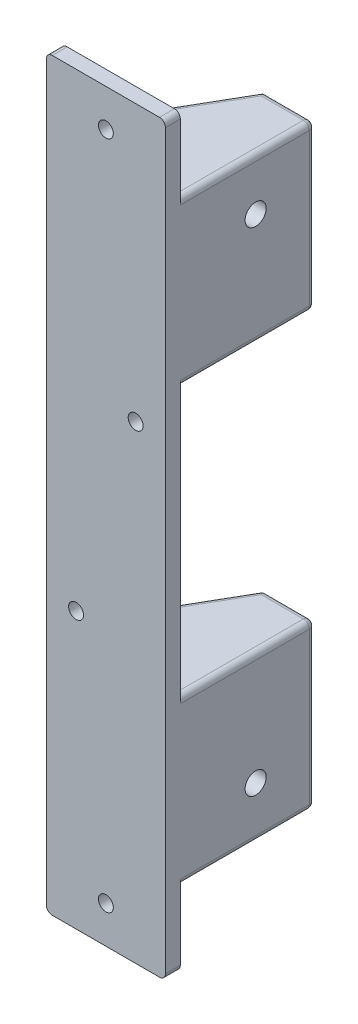
SolidWorks part; units mm, degrees
material "ABS"
ref_plane "X-Y Datum" through (0, 0, 0) normal (0, 0, 1) x (1, 0, 0)
ref_plane "X-Z Datum" through (0, 0, 0) normal (0, 1, 0) x (1, 0, 0)
ref_plane "Y-Z Datum" through (0, 0, 0) normal (1, 0, 0) x (0, 0, -1)
sketch "Sketch1" plane through (0, 0, 0) normal (0, 1, 0) x (1, 0, 0)
  line L0 (0, 0) -> (-25.4, 0)
  line L1 (-25.4, 0) -> (-25.4, 6.985)
  line L2 (-25.4, 6.985) -> (0, 50.9791)
  line L3 (0, 50.9791) -> (0, 0)
  dimension "D1" = 25.4
  dimension "D2" = 60
  dimension "D3" = 6.985
extrude "Boss-Extrude1" add sketch "Sketch1" along normal blind 127
ref_plane "Plane1" through (0, 63.5, 0) normal (0, -1, 0) x (-1, 0, 0)
sketch "Sketch2" plane through (0, 63.5, 0) normal (0, -1, 0) x (-1, 0, 0)
  line L0 (3.175, 3.175) -> (25.4, 3.175)
  line L2 (25.4, 3.175) -> (25.4, 6.985)
  line L3 (25.4, 6.985) -> (3.175, 45.4798)
  line L4 (3.175, 45.4798) -> (3.175, 3.175)
  line L5 (25.4, 3.175) -> (25.4, 0) construction
  line L6 (25.4, 0) -> (0, 0) construction
  line L7 (25.4, 6.985) -> (25.4, 0) construction
  line L9 (0, 50.9791) -> (25.4, 6.985) construction
  line L10 (0, 50.9791) -> (25.4, 6.985) construction
  line L11 (3.175, 3.175) -> (0, 3.175)
  line L12 (0, 0) -> (0, 50.9791) construction
  dimension "D1" = 3.175
extrude "Cut-Extrude1" cut sketch "Sketch2" against normal offset from surface (28.575 mm away) 3.175 from offset 31.75 contours L3 L4 L0 L2 region at (-11.1954, 63.5, -17.3815) up to face at (-12.7, 127, -14.491) offset against normal yes
extrude "Cut-Extrude2" cut sketch "Sketch2<2>" along normal offset from surface (28.575 mm away) 3.175 from offset 31.75 contours L3 L4 L0 L2 region at (-11.1954, 63.5, -17.3815) up to face at (-12.7, 0, -14.491)
sketch "Sketch2<2>" plane through (0, 63.5, 0) normal (0, -1, 0) x (-1, 0, 0) same geometry as "Sketch2"
sketch "Sketch3" plane through (0, 63.5, 0) normal (0, -1, 0) x (-1, 0, 0)
  line L0 (0, 0) -> (0, 45.4798) construction
  line L1 (25.4, 3.175) -> (0, 3.175)
  line L2 (25.4, 3.175) -> (25.4, 53.975)
  line L3 (25.4, 53.975) -> (0, 53.975)
  line L4 (0, 3.175) -> (0, 53.975)
  line L5 (25.4, 3.175) -> (25.4, 6.985) construction
  line L6 (25.4, 3.175) -> (3.175, 3.175) construction
  dimension "D1" = 50.8
extrude "Cut-Extrude4" cut sketch "Sketch3" against normal mid plane 57.15
sketch "Sketch6" plane through (0, 0, 0) normal (0, -1, 0) x (1, 0, 0)
  line L0 (0, -31.9291) -> (0, -50.9791)
  line L1 (0, 0) -> (0, -50.9791) construction
  line L2 (0, -50.9791) -> (-10.9985, -31.9291)
  line L3 (0, -50.9791) -> (-25.4, -6.985) construction
  line L4 (-10.9985, -31.9291) -> (0, -31.9291)
  dimension "D1" = 19.05
extrude "Cut-Extrude7" cut sketch "Sketch6" against normal through all both and the other way through all
sketch "Sketch5" plane through (0, 0, -3.175) normal (0, 0, -1) x (-1, 0, 0)
  line L0 (0, 63.5) -> (25.4, 63.5) construction
  line L1 (6.35, 84.1375) -> (19.05, 84.1375) construction
  line L2 (6.35, 84.1375) -> (6.35, 42.8625) construction
  line L3 (6.35, 42.8625) -> (19.05, 42.8625) construction
  line L4 (19.05, 84.1375) -> (19.05, 42.8625) construction
  line L5 (6.35, 84.1375) -> (19.05, 42.8625) construction
  line L6 (6.35, 42.8625) -> (19.05, 84.1375) construction
  line L7 (0, 92.075) -> (0, 34.925) construction
  line L8 (25.4, 92.075) -> (25.4, 34.925) construction
  circle A0 centre (6.35, 84.1375) radius 1.5875
  circle A1 centre (19.05, 42.8625) radius 1.5875
  point P0 (12.7, 63.5)
  point P6 (12.7, 63.5)
  dimension "D3" = 3.175
  dimension "D1" = 12.7
  dimension "D2" = 41.275
extrude "Cut-Extrude6" cut sketch "Sketch5" against normal through all both and the other way through all
sketch "Sketch8" plane through (-3.175, 0, 0) normal (-1, 0, 0) x (0, 0, 1)
  line L0 (-19.2291, 11) -> (-19.2291, 116) construction
  line L1 (-13.2715, 63.5) -> (13.2715, 63.5) construction
  line L2 (-31.9291, 3.175) -> (-31.9291, 31.75) construction
  circle A0 centre (-19.2291, 11) radius 2.25
  circle A1 centre (-19.2291, 116) radius 2.25
  point P4 (-19.2291, 63.5)
  dimension "D2" = 4.5
  dimension "D1" = 105
  dimension "D3" = 12.7
extrude "Cut-Extrude9" cut sketch "Sketch8" against normal through all both and the other way through all
sketch "Sketch9" plane through (0, 0, 0) normal (0, 0, 1) x (1, 0, 0)
  line L0 (-25.4, 92.075) -> (-25.4, 34.925) construction
  line L1 (0, 0) -> (-25.4, 0)
  line L2 (0, 0) -> (0, -15.875)
  line L3 (0, -15.875) -> (-25.4, -15.875)
  line L4 (-25.4, 0) -> (-25.4, -15.875)
  line L5 (-12.7, -15.875) -> (-12.7, -7.9375) construction
  line L6 (-12.7, -7.9375) -> (0, -7.9375) construction
  line L7 (-13.2715, 63.5) -> (13.2715, 63.5) construction
  line L8 (-12.7, 134.9375) -> (0, 134.9375) construction
  line L9 (-12.7, 142.875) -> (-12.7, 134.9375) construction
  line L10 (-25.4, 127) -> (-25.4, 142.875)
  line L11 (0, 142.875) -> (-25.4, 142.875)
  line L12 (0, 127) -> (0, 142.875)
  line L13 (0, 127) -> (-25.4, 127)
  circle A0 centre (-12.7, -7.9375) radius 1.5875
  circle A1 centre (-12.7, 134.9375) radius 1.5875
  dimension "D2" = 3.175
  dimension "D1" = 15.875
extrude "Boss-Extrude2" add sketch "Sketch9" against normal blind 3.175
fillet "Fillet1" radius 1.27 32 edges at (-14.2875, 123.825, -3.175) (-3.175, 123.825, -17.552) (-14.2875, 31.75, -3.175) (-3.175, 31.75, -17.552) (-3.175, 109.5375, -3.175) (-14.2875, 95.25, -3.175) (-3.175, 17.4625, -3.175) (-14.2875, 3.175, -3.175) (-3.175, 95.25, -17.552) (-3.175, 3.175, -17.552) (0, 34.925, -17.552) (0, -15.875, -1.5875) (-5.4993, 0, -31.9291) (-18.1993, 0, -19.457) (-25.4, 0, -5.08) (0, 142.875, -1.5875) (-25.4, 142.875, -1.5875) (-25.4, -15.875, -1.5875) (0, 17.4625, -31.9291) (0, 109.5375, -31.9291) (0, 92.075, -17.552) (0, 127, -17.552) (0, 0, -17.552) (-5.4993, 127, -31.9291) (-18.1993, 127, -19.457) (-25.4, 127, -5.08) (-5.4993, 92.075, -31.9291) (-18.1993, 92.075, -19.457) (-25.4, 92.075, -5.08) (-5.4993, 34.925, -31.9291) (-18.1993, 34.925, -19.457) (-25.4, 34.925, -5.08)
